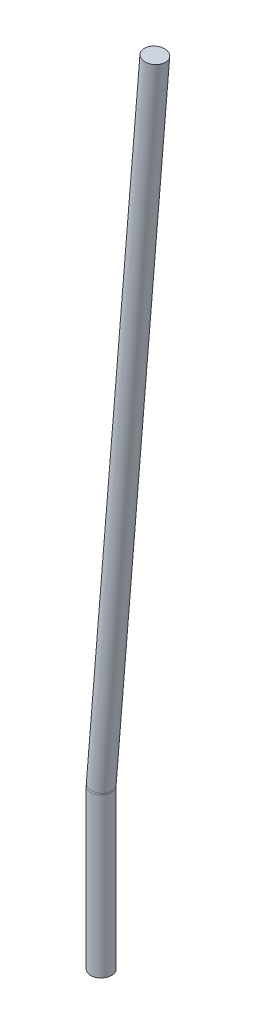
SolidWorks part; units mm, degrees
material "3.0517 (EN-AW 3003)"
ref_plane "Front" through (0, 0, 0) normal (0, 0, 1) x (1, 0, 0)
ref_plane "Top" through (0, 0, 0) normal (0, 1, 0) x (1, 0, 0)
ref_plane "Right" through (0, 0, 0) normal (1, 0, 0) x (0, 0, -1)
sketch "Sketch1" plane through (0, 0, 0) normal (0, 1, 0) x (1, 0, 0)
  circle A0 centre (0, 0) radius 0.2
  dimension "D1" = 0.4
extrude "Boss-Extrude1" add sketch "Sketch1" against normal blind 3
sketch "Sketch2" plane through (0, 0, 0) normal (0, 1, 0) x (1, 0, 0)
  line L0 (0.5, 0.2) -> (0.5, -0.2) construction
  circle A1 centre (0, 0) radius 0.2
  circle A2 centre (0, 0) radius 0.2
  point P5 (0.5, 0)
  dimension "D2" = 0.4
  dimension "D3" = 0.5
  dimension "D1" = 0
revolve "Revolve1" add sketch "Sketch2" angle 4.66 about L0 reverse direction yes
sketch "Sketch3" plane through (0.0033, 0.0405, 0) normal (0.0812, 0.9967, 0) x (0.9967, -0.0812, 0)
  circle A1 centre (-0.0017, 0) radius 0.2
  circle A2 centre (-0.0017, 0) radius 0.2
  dimension "D1" = 0
extrude "Boss-Extrude2" add sketch "Sketch3" along normal blind 12.5
